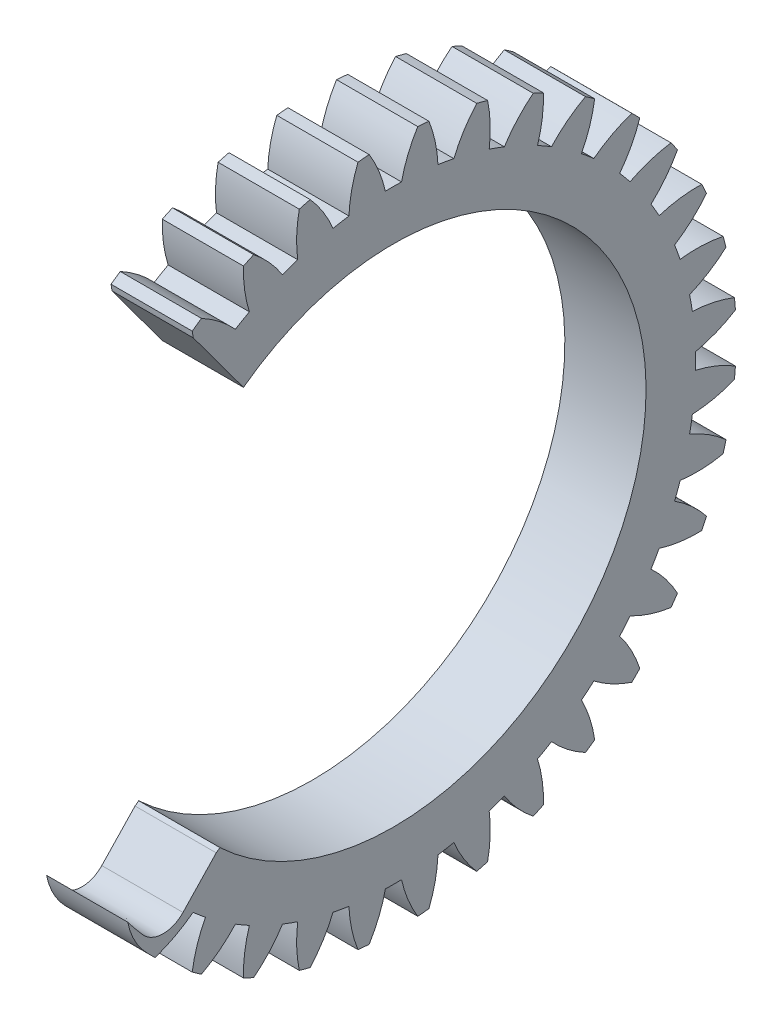
SolidWorks part; units mm, degrees
ref_plane "Plane1" through (0, 0, 0) normal (0, 0, 1) x (1, 0, 0)
ref_plane "Plane2" through (0, 0, 0) normal (0, 1, 0) x (1, 0, 0)
ref_plane "Plane3" through (0, 0, 0) normal (1, 0, 0) x (0, 0, -1)
sketch "HoldingSke" plane through (0, 0, 0) normal (0, 1, 0) x (1, 0, 0)
  line L0 (0, 0) -> (0.4045, -0.2939)
  line L1 (-15, 0) -> (100, 0) construction
  line L2 (0, 0) -> (-2.1039, 2.3779)
  line L3 (0, 0) -> (-11.863, 4.5341)
  line L4 (0, 0) -> (6.9867, 5.0761)
  line L5 (0, 0) -> (-46.8476, -17.4728)
  line L6 (0, 0) -> (-7.4607, -5.0337)
  line L7 (-2.1039, 2.3779) -> (8.6586, 51.2059)
  line L8 (-76.2, 54.61) -> (-71.9, 54.61)
  line L9 (-71.009, 38.7566) -> (-53.1078, 45.2721)
  line L10 (-76.2, 71.12) -> (104.1128, 71.12)
  line L11 (0, 0) -> (-9, 0)
  line L12 (-76.2, 101.6) -> (-76.133, 101.6)
  line L13 (24.9733, 27.94) -> (52.9518, 28.4284)
  line L14 (24.9733, 27.94) -> (24.9743, 27.94)
  line L15 (24.9733, 27.94) -> (100.4006, 29.5858)
  line L16 (-63.627, -2) -> (-12.827, -2)
  circle A0 centre (0, 0) radius 28
  circle A1 centre (0, 0) radius 33.499
  circle A2 centre (0, 0) radius 37.5
  circle A3 centre (0, 0) radius 28
  dimension "Num_teeth" = 36
  dimension "Pitch_radius" = 180.3128
  dimension "Width" = 9
  dimension "Thickness" = 9
sketch "BasProSke" plane through (0, 0, 0) normal (0, 1, 0) x (1, 0, 0)
  line L0 (-10, 0) -> (60, 0) construction
  line L1 (0, 0) -> (0, 38)
  line L2 (0, 0) -> (9, 0)
  line L3 (9, 0) -> (9, 38)
  line L4 (9, 38) -> (0, 38)
  dimension "Thickness" = 9
  dimension "Diameter" = 76
revolve "Base-Revolve" add sketch "BasProSke" angle 360 about L0
sketch "TooCutSke" plane through (0, 0, 0) normal (1, 0, 0) x (0, 0, -1)
  line L1 (0, 0) -> (0, 107) construction
  line L2 (0, 0) -> (-1.6875, 35.9604) construction
  line L3 (0, 0) -> (-6.2701, 71.6676) construction
  line L4 (-1.6875, 35.9604) -> (-3.135, 35.8338) construction
  arc A0 (0.8949, 33.487) -> (-0.8949, 33.487) centre (0, 0) ccw
  arc A1 (2.7061, 37.929) -> (-2.7061, 37.929) centre (0, 0) ccw
  circle A2 centre (0, 0) radius 36 construction
  circle A3 centre (0, 0) radius 33.8289 construction
  arc A4 (-0.8949, 33.487) -> (-2.7061, 37.929) centre (-14.9484, 30.347) ccw
  arc A5 (2.7061, 37.929) -> (0.8949, 33.487) centre (14.9484, 30.347) ccw
extrude "ToothCut" cut sketch "TooCutSke" along normal through all
fillet "Breaks" [suppressed] radius 0.04 tangent propagation no
fillet "RootFillets" [suppressed] radius 0.501
pattern_circular "TeethCuts" count 36 every 10 about axis through (-10, 0, 0) along (1, 0, 0) of "ToothCut", "RootFillets", "Breaks"
sketch "HubNeaOneSke" plane through (0, 0, 0) normal (-1, 0, 0) x (0, 0, 1)
  circle A0 centre (0, 0) radius 33.499
  dimension "Diameter" = 66.998
extrude "HubNearOne" [suppressed] add sketch "HubNeaOneSke" along normal blind 41.0001
sketch "HubNeaBotSke" plane through (0, 0, 0) normal (-1, 0, 0) x (0, 0, 1)
  circle A0 centre (0, 0) radius 33.499
  dimension "Diameter" = 66.998
extrude "HubNearBoth" [suppressed] add sketch "HubNeaBotSke" along normal blind 20.5
ref_plane "FarPln" through (9, 0, 0) normal (1, 0, 0) x (0, 0, -1)
sketch "HubFarSke" plane through (9, 0, 0) normal (1, 0, 0) x (0, 0, -1)
  circle A0 centre (0, 0) radius 33.499
  dimension "Diameter" = 66.998
extrude "HubFar" [suppressed] add sketch "HubFarSke" along normal blind 20.5
sketch "BorSke" plane through (0, 0, 0) normal (1, 0, 0) x (0, 0, -1)
  circle A0 centre (0, 0) radius 28
  dimension "Diameter" = 56
extrude "Bore" cut sketch "BorSke" along normal mid plane 100.0001
sketch "KeySke" plane through (0, 0, 0) normal (1, 0, 0) x (0, 0, -1)
  line L0 (-8, 0) -> (-8, 32.3)
  line L1 (-8, 32.3) -> (8, 32.3)
  line L2 (8, 32.3) -> (8, 0)
  line L3 (0, 0) -> (0, 34) construction
  line L4 (-8, 0) -> (8, 0)
  dimension "Width" = 16
extrude "Keyway" [suppressed] cut sketch "KeySke" along normal mid plane 100.0001
pattern_circular "Keyway2" [suppressed] count 2 every 90 about axis through (-10, 0, 0) along (1, 0, 0) reverse direction yes
sketch "Szkic1" plane through (0, 0, 0) normal (1, 0, 0) x (0, 0, -1)
  line L0 (0, 0) -> (-27.328, 37.0259)
  line L1 (-27.328, 37.0259) -> (-47.6164, -10.233)
  line L2 (-47.6164, -10.233) -> (0, 0)
extrude "Wytnij-wyciągnięcie1" cut sketch "Szkic1" along normal through all
sketch "Szkic2" plane through (0, 0, 0) normal (1, 0, 0) x (0, 0, -1)
  line L0 (-19.6433, -20.6493) -> (-23.3286, -24.5233) construction
  line L1 (-19.6433, -20.6493) -> (-23.3286, -24.5233)
  line L2 (-24.5118, 27.7159) -> (-14.2182, -16.6493)
  line L3 (-14.2182, -16.6493) -> (-19.6433, -20.6493)
  line L4 (-24.5118, 27.7159) -> (-50.9594, 25.255)
  line L5 (-50.9594, 25.255) -> (-37.7356, -29.3697)
  line L6 (-37.7356, -29.3697) -> (-27.7664, -24.4546)
  line L7 (-26.426, -27.3069) -> (-27.3069, -26.426)
  line L8 (-26.426, -27.3069) -> (-25.0675, -25.4318)
  arc A0 (-24.5118, 27.7159) -> (-27.7664, -24.4546) centre (0, 0) ccw construction
  arc A1 (-24.5118, 27.7159) -> (-27.7664, -24.4546) centre (0, 0) ccw
  arc A2 (-27.3069, -26.426) -> (-29.4473, -22.4022) centre (-21.7924, -20.9115) cw
  spline S0 degree 3 poles (349821.6663, 433515.9451) (9018.2404, 11711.6889) (-165.7366, 78.0978) (-27.1426, -24.9996) (-26.9606, -25.1074) (-26.5829, -25.2806) (-26.3868, -25.3469) (-25.9801, -25.4387) (-25.7711, -25.4633) (-25.3572, -25.469) (-25.1483, -25.4503) (-24.7384, -25.37) (-24.5404, -25.3094) (-24.158, -25.1482) (-23.9725, -25.0463) (129.087, 80.8249) (-9985.0363, 13604.9554) (-338251.7622, 442935.714) knots -103.998447 -103.998447 -103.998447 -103.998447 0.125 0.125 0.25 0.25 0.375 0.375 0.5 0.5 0.625 0.625 0.75 0.75 0.875 0.875 112.838295 112.838295 112.838295 112.838295 only from (-27.7664, -24.4546) to (-23.3286, -24.5233) construction
  spline S1 degree 3 poles (-27.7664, -24.4546) (-27.6277, -24.6121) (-27.4749, -24.7523) (-27.1426, -24.9996) (-26.9606, -25.1074) (-26.5829, -25.2806) (-26.3868, -25.3469) (-25.9801, -25.4387) (-25.7711, -25.4633) (-25.3572, -25.469) (-25.1483, -25.4503) (-24.7384, -25.37) (-24.5404, -25.3094) (-24.158, -25.1482) (-23.9725, -25.0463) (-23.6312, -24.8102) (-23.4733, -24.6754) (-23.3286, -24.5233) knots 0 0 0 0 0.125 0.125 0.25 0.25 0.375 0.375 0.5 0.5 0.625 0.625 0.75 0.75 0.875 0.875 1 1 1 1
extrude "Wytnij-wyciągnięcie2" cut sketch "Szkic2" against normal blind 43 and the other way through all contours A1 L4 L5 L6 | A1 S1 L1 L3 L2 region at (0, -1.5762, 26.5296) region at (0, 4.8425, 39.1923)
extrude "Dodanie-wyciągnięcie1" add sketch "Szkic2<3>" along normal up to surface (9 mm away) contours A2 L6 A1 | S1 L6 A2 L7 L8 region at (0, -25.7946, 26.8655) region at (0, -23.8723, 28.649) up to face at (9, -1.2954, -9.9994)
sketch "Szkic2<3>" plane through (0, 0, 0) normal (1, 0, 0) x (0, 0, -1) same geometry as "Szkic2"
equation "' \"Module@HoldingSke\" = 6.35"
equation "' \"Num_teeth@HoldingSke\" = 12"
equation "' \"Ap@HoldingSke\" =  20"
equation "' \"Ap@HoldingSke\" = 20"
equation "' \"Width@HoldingSke\" = 0.5 * 25.4"
equation "' \"Hub_dia@HoldingSke\"= 1 * 25.4"
equation "' \"Hub_dia@HoldingSke\" = 1 * 25.4"
equation "' \"Overall_len@HoldingSke\" = 1.0 * 25.4"
equation "' \"Bore@HoldingSke\" = 0.75 * 25.4"
equation "' \"T_dim@HoldingSke\" = 0.1 * 25.4"
equation "' \"Width@KeySke\" = 0.25 * 25.4"
equation "' \"Show_teeth@HoldingSke\" = 13"
equation "' \"Backlash@HoldingSke\" = 0.009 * 25.4"
equation "' \"Addendum_fac@HoldingSke\" = 1.0"
equation "' \"Dedendum_fac@HoldingSke\" = 1.25"
equation "' \"Dedendum_add@HoldingSke\" = 0.00005 * 25.4"
equation "' \"Clearance_fac@HoldingSke\" = 0.25"
equation "\"Pitch@HoldingSke\" = 1 / \"Module@HoldingSke\""
equation "\"Overcut_dia@TooCutSke\" = (\"Num_teeth@HoldingSke\" + 2 * \"Addendum_fac@HoldingSke\") / \"Pitch@HoldingSke\" + 0.002 * 25.4"
equation "\"Pitch_dia@TooCutSke\" = \"Num_teeth@HoldingSke\" / \"Pitch@HoldingSke\""
equation "\"Base_dia@TooCutSke\" = \"Num_teeth@HoldingSke\" / \"Pitch@HoldingSke\" * cos((\"Ap@HoldingSke\"  * 3.14159265 / 180))"
equation "\"Root_dia@TooCutSke\" = (\"Num_teeth@HoldingSke\" + 2) / \"Pitch@HoldingSke\" - 2 * (\"Addendum_fac@HoldingSke\" + \"Dedendum_fac@HoldingSke\") / \"Pitch@HoldingSke\" - \"Dedendum_add@HoldingSke\" * 2"
equation "\"Half_ang@TooCutSke\" = 180 / \"Num_teeth@HoldingSke\""
equation "\"Half_CT@TooCutSke\" = \"Num_teeth@HoldingSke\" / \"Pitch@HoldingSke\" * sin((3.14159265 / 2 / \"Num_teeth@HoldingSke\")) / 2 - 7 * \"Backlash@HoldingSke\" / 4"
equation "\"Flank_rad@TooCutSke\" = \"Num_teeth@HoldingSke\" / \"Pitch@HoldingSke\" / 5"
equation "\"Radius@RootFillets\" = \"Clearance_fac@HoldingSke\" / \"Pitch@HoldingSke\" + \"Dedendum_add@HoldingSke\""
equation "\"Break_rad@Breaks\" = 0.02 / \"Pitch@HoldingSke\""
equation "\"Thickness@HoldingSke\" = \"Width@HoldingSke\""
equation "\"OAL@HoldingSke\" = \"Thickness@HoldingSke\""
equation "\"MHD@HoldingSke\" = (\"Num_teeth@HoldingSke\" + 2) / \"Pitch@HoldingSke\" - 2 * (\"Addendum_fac@HoldingSke\" + \"Dedendum_fac@HoldingSke\")  / \"Pitch@HoldingSke\" - \"Dedendum_add@HoldingSke\" * 2"
equation "\"MBD@HoldingSke\" = (\"Num_teeth@HoldingSke\" + 2) / \"Pitch@HoldingSke\" - 2 * (\"Addendum_fac@HoldingSke\" + \"Dedendum_fac@HoldingSke\")  / \"Pitch@HoldingSke\" - \"Dedendum_add@HoldingSke\" * 2 - 0.002 * 25.4"
equation "\"MHD@HoldingSke\" = ((sgn( \"MHD@HoldingSke\" - \"Hub_dia@HoldingSke\" )-1)*( \"MHD@HoldingSke\" - \"Hub_dia@HoldingSke\" ))/-2+ \"Hub_dia@HoldingSke\""
equation "\"MBD@HoldingSke\" = ((sgn( \"MBD@HoldingSke\" - \"Bore@HoldingSke\" )-1)*( \"MBD@HoldingSke\" - \"Bore@HoldingSke\" ))/-2+ \"Bore@HoldingSke\""
equation "\"OAL@HoldingSke\" = ((sgn( \"OAL@HoldingSke\" - \"Overall_len@HoldingSke\" )+1)*( \"OAL@HoldingSke\" - \"Overall_len@HoldingSke\" ))/2 + \"Overall_len@HoldingSke\" + 0.000002 * 25.4"
equation "\"Num_teeth@TeethCuts\" = int( \"Show_teeth@HoldingSke\" ) + 1"
equation "\"Num_teeth@TeethCuts\" = ((sgn( \"Num_teeth@TeethCuts\" - \"Num_teeth@HoldingSke\" )-1)*( \"Num_teeth@TeethCuts\" - \"Num_teeth@HoldingSke\" ))/-2+ \"Num_teeth@HoldingSke\""
equation "\"Num_teeth@TeethCuts\" = ((sgn( \"Num_teeth@TeethCuts\" - 2.0)+1)*( \"Num_teeth@TeethCuts\" - 2.0))/2 +2.0"
equation "\"Angle@TeethCuts\" = 360.0 / \"Num_teeth@HoldingSke\""
equation "\"Diameter@BasProSke\" = (\"Num_teeth@HoldingSke\" + 2 * \"Addendum_fac@HoldingSke\") / \"Pitch@HoldingSke\""
equation "\"Thickness@BasProSke\"  = \"Thickness@HoldingSke\""
equation "' \"Fillet_rad@BasProSke\" =  \"Thickness@HoldingSke\" * 0.05"
equation "' \"Fillet_rad@BasProSke\" = \"Thickness@HoldingSke\" * 0.05"
equation "\"MHD@HoldingSke\" = ((sgn( \"MHD@HoldingSke\" - \"Root_dia@TooCutSke\" )-1)*( \"MHD@HoldingSke\" - \"Root_dia@TooCutSke\" ))/-2+ \"Root_dia@TooCutSke\""
equation "\"Diameter@HubNeaOneSke\" = \"MHD@HoldingSke\""
equation "\"Length@HubNearOne\" = \"OAL@HoldingSke\" - \"Thickness@BasProSke\""
equation "\"Diameter@HubNeaBotSke\" = \"MHD@HoldingSke\""
equation "\"Length@HubNearBoth\" = ( \"OAL@HoldingSke\" - \"Thickness@BasProSke\" ) / 2.0"
equation "\"Thickness@FarPln\" = \"Thickness@BasProSke\""
equation "\"Diameter@HubFarSke\" = \"MHD@HoldingSke\""
equation "\"Length@HubFar\" = ( \"OAL@HoldingSke\" - \"Thickness@BasProSke\" ) / 2.0"
equation "\"Diameter@BorSke\" = \"MBD@HoldingSke\""
equation "\"D1@Bore\" = \"OAL@HoldingSke\" * 2.0"
equation "\"D1@Keyway\" = \"OAL@HoldingSke\" * 2.0"
equation "\"Offset@KeySke\" = \"T_dim@HoldingSke\" + \"MBD@HoldingSke\" / 2.0"
